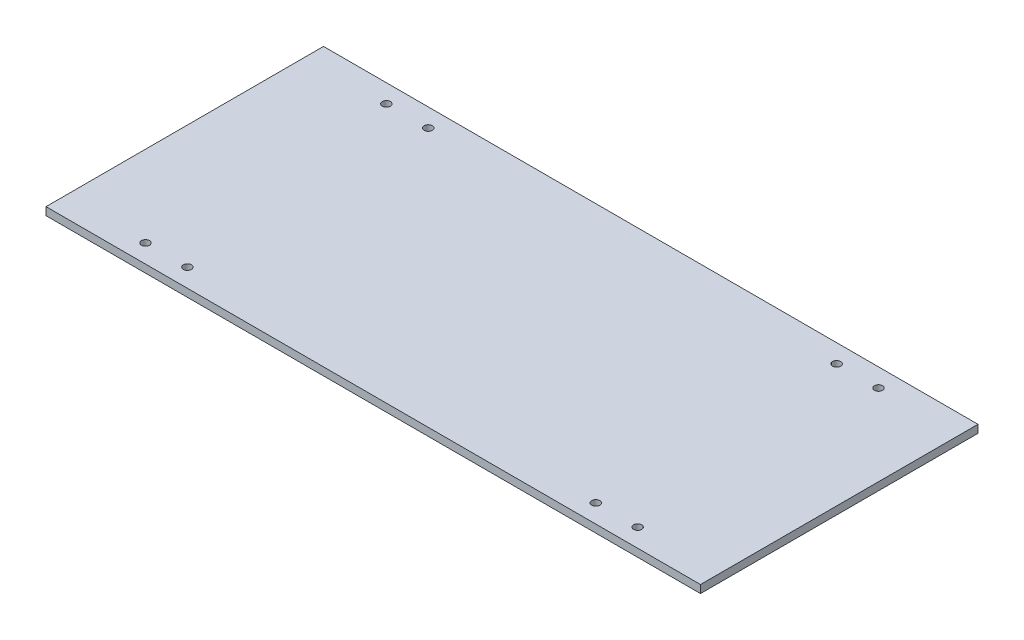
SolidWorks part; units mm, degrees
ref_plane "Front Plane" through (0, 0, 0) normal (0, 0, 1) x (1, 0, 0)
ref_plane "Top Plane" through (0, 0, 0) normal (0, 1, 0) x (1, 0, 0)
ref_plane "Right Plane" through (0, 0, 0) normal (1, 0, 0) x (0, 0, -1)
sketch "Sketch1" plane through (0, 0, 0) normal (0, 1, 0) x (1, 0, 0)
  line L0 (125, 106) -> (125, 0) construction
  line L1 (0, 106) -> (250, 106)
  line L2 (0, 106) -> (0, 0)
  line L3 (0, 0) -> (250, 0)
  line L4 (250, 106) -> (250, 0)
  line L5 (0, 53) -> (250, 53) construction
  circle A0 centre (31, 99) radius 1.55
  circle A1 centre (47, 99) radius 1.55
  circle A2 centre (203, 99) radius 1.55
  circle A3 centre (219, 99) radius 1.55
  circle A4 centre (219, 7) radius 1.55
  circle A5 centre (203, 7) radius 1.55
  circle A6 centre (47, 7) radius 1.55
  circle A7 centre (31, 7) radius 1.55
  dimension "D2" = 3.1
  dimension "D1" = 250
  dimension "D3" = 16
  dimension "D5" = 7
  dimension "D6" = 99
  dimension "D4" = 78
extrude "Boss-Extrude1" add sketch "Sketch1" along normal blind 3
equation "\"cf_tube_outer_diameter\"= 25mm"
equation "\"cf_tube_inner_diameter\" = 21mm"
equation "\"mid_plate_mid_to_top\" = 100mm"
equation "\"mid_plate_mid_to_bottom\" = 30mm"
equation "\"mid_plate_horizontal_spacing\"=250mm"
equation "\"cf_plate_thickness\" =3mm"
equation "\"mid_tube_length\" = 500mm"
equation "\"mid_support_plate_distance\" = 250mm"
equation "\"M3_hole_diameter\" = 3.1mm"
equation "\" cf_tube_outer_diameter\"= 25mm"
equation "\"D2@Sketch1\"=\"M3_hole_diameter\""
